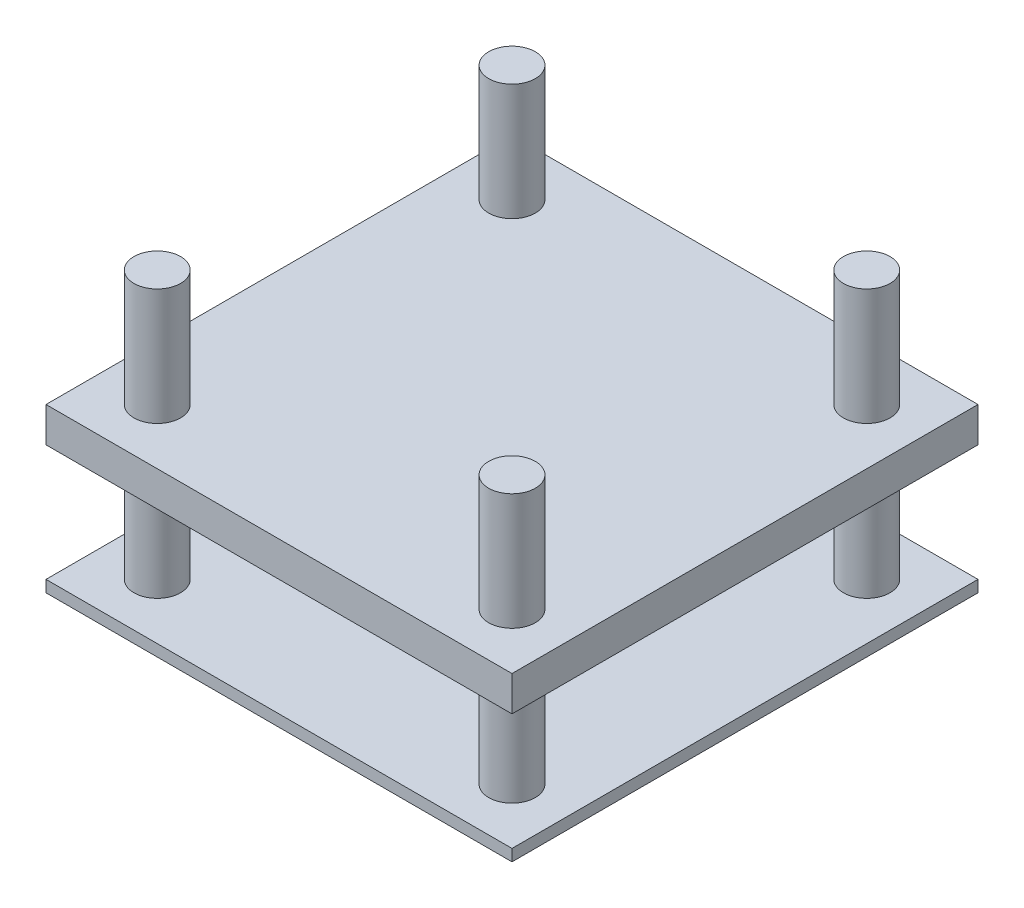
SolidWorks part; units mm, degrees
ref_plane "前视基准面" through (0, 0, 0) normal (0, 0, 1) x (1, 0, 0)
ref_plane "上视基准面" through (0, 0, 0) normal (0, 1, 0) x (1, 0, 0)
ref_plane "右视基准面" through (0, 0, 0) normal (1, 0, 0) x (0, 0, -1)
sketch "草图2" plane through (0, 0, 0) normal (0, 1, 0) x (1, 0, 0)
  line L0 (0, 0) -> (31.047, 0) construction
  line L1 (-9.75, -9.75) -> (9.75, -9.75)
  line L2 (-9.75, -9.75) -> (-9.75, 9.75)
  line L3 (-9.75, 9.75) -> (9.75, 9.75)
  line L4 (9.75, -9.75) -> (9.75, 9.75)
  line L5 (-9.75, -9.75) -> (9.75, 9.75) construction
  line L6 (-9.75, 9.75) -> (9.75, -9.75) construction
  line L7 (-20, -20) -> (20, -20)
  line L8 (-20, -20) -> (-20, 20)
  line L9 (-20, 20) -> (20, 20)
  line L10 (20, -20) -> (20, 20)
  line L11 (-20, -20) -> (20, 20) construction
  line L12 (-20, 20) -> (20, -20) construction
  line L13 (0, 0) -> (0, 17.7315) construction
  circle A0 centre (15.2248, 15.2248) radius 2
  circle A1 centre (-15.2248, -15.2248) radius 2
  circle A2 centre (15.2248, -15.2248) radius 2
  circle A3 centre (-15.2248, 15.2248) radius 2
  point P0 (0, 0)
  point P6 (0, 0)
  dimension "D5" = 4
  dimension "D1" = 19.5
  dimension "D2" = 19.5
  dimension "D3" = 40
  dimension "D4" = 40
  dimension "D6" = 21.5311
extrude "凸台-拉伸2" add sketch "草图2" along normal blind 1 contours L8 L9 L10 L7
sketch "草图3" plane through (0, 0, 0) normal (0, 1, 0) x (1, 0, 0)
  circle A0 centre (-15.2248, -15.2248) radius 2 construction
  circle A1 centre (15.2248, -15.2248) radius 2 construction
  circle A2 centre (15.2248, 15.2248) radius 2 construction
  circle A3 centre (-15.2248, 15.2248) radius 2 construction
  circle A4 centre (-15.2248, -15.2248) radius 2
  circle A5 centre (15.2248, -15.2248) radius 2
  circle A6 centre (15.2248, 15.2248) radius 2
  circle A7 centre (-15.2248, 15.2248) radius 2
extrude "切除-拉伸1" cut sketch "草图3" along normal blind 3
sketch "草图4" plane through (0, 0, 0) normal (0, 1, 0) x (1, 0, 0)
  line L0 (0, 0) -> (31.047, 0) construction
  circle A0 centre (3, 0) radius 2
  dimension "D1" = 4
  dimension "D2" = 3
sketch "草图9" plane through (0, 1, 0) normal (0, 1, 0) x (1, 0, 0)
  line L1 (20, -20) -> (-20, -20)
  line L2 (20, -20) -> (20, 20)
  line L3 (20, 20) -> (-20, 20)
  line L4 (-20, -20) -> (-20, 20)
extrude "凸台-拉伸4" add sketch "草图9" along normal blind 3 from offset 10 separate body
extrude "凸台-拉伸5" add sketch "草图3<3>" along normal blind 24 contours A4 | A7 | A6 | A5
sketch "草图3<3>" plane through (0, 0, 0) normal (0, 1, 0) x (1, 0, 0) same geometry as "草图3"
cosmetic thread "装饰螺纹线5" parameters "D2"=3.242
cosmetic thread "装饰螺纹线6" parameters "D2"=3.242
cosmetic thread "装饰螺纹线7" parameters "D2"=3.242
cosmetic thread "装饰螺纹线8" parameters "D2"=3.242
cosmetic thread "装饰螺纹线9" parameters "D2"=3.242
cosmetic thread "装饰螺纹线10" parameters "D2"=3.242
cosmetic thread "装饰螺纹线11" parameters "D2"=3.242
extrude "凸台-拉伸6" add sketch "草图2<8>" against normal blind 2 contours A0 | A3 | A1 | A2
sketch "草图2<8>" plane through (0, 0, 0) normal (0, 1, 0) x (1, 0, 0) same geometry as "草图2"
sketch "草图11" plane through (0, 11, 0) normal (0, -1, 0) x (1, 0, 0)
  line L1 (-14.325, -7.9352) -> (14.325, -7.9352)
  line L2 (-14.325, -7.9352) -> (-14.325, 7.9352)
  line L3 (-14.325, 7.9352) -> (14.325, 7.9352)
  line L4 (14.325, -7.9352) -> (14.325, 7.9352)
  line L5 (-14.325, -7.9352) -> (14.325, 7.9352) construction
  line L6 (-14.325, 7.9352) -> (14.325, -7.9352) construction
  point P0 (0, 0)
sketch "草图12" plane through (0, 1, 0) normal (0, 1, 0) x (1, 0, 0)
  circle A0 centre (-7, 0) radius 5.125 construction
  circle A1 centre (-7, 0) radius 5.125
sketch "草图16" plane through (0, 0, 0) normal (1, 0, 0) x (0, 0, -1)
  circle A0 centre (-4.3167, -2.2841) radius 0.8937
  circle A1 centre (-0.9811, -2.2841) radius 0.8937
  circle A2 centre (1.6678, -2.2841) radius 0.8937
  circle A3 centre (4.611, -2.2841) radius 0.8937
extrude "切除-拉伸2" cut sketch "草图2<9>" along normal blind 10 contours L4 L3 L2 L1
sketch "草图2<9>" plane through (0, 0, 0) normal (0, 1, 0) x (1, 0, 0) same geometry as "草图2"
